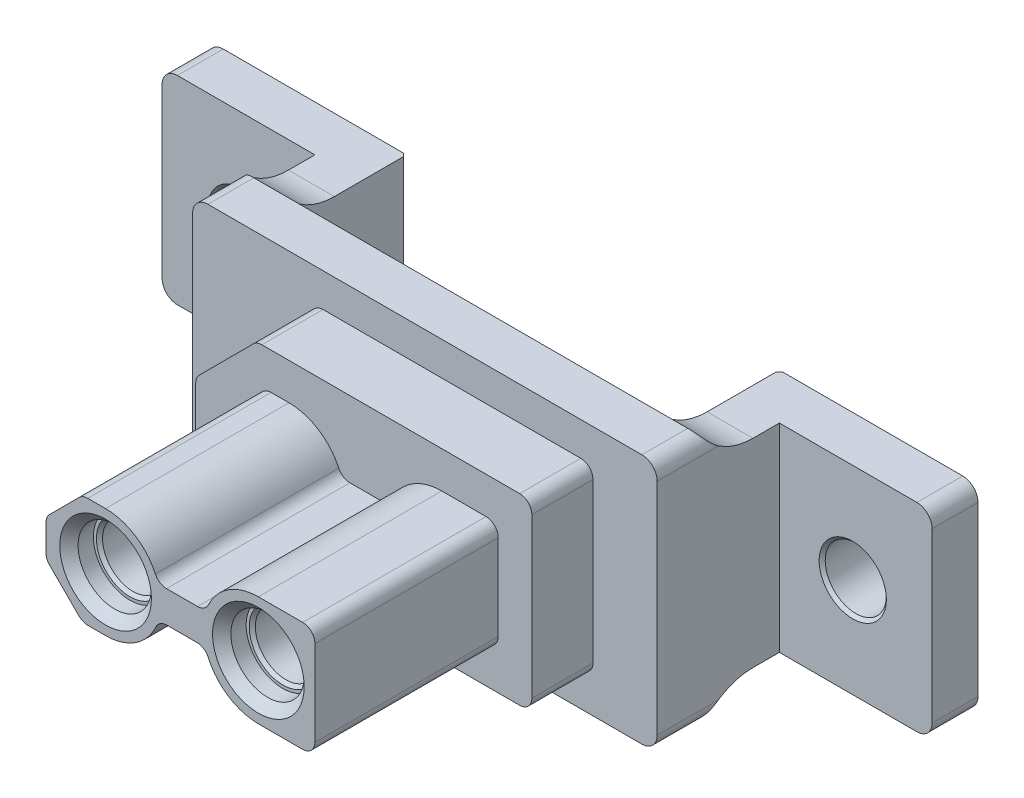
SolidWorks part; units mm, degrees
ref_plane "Спереди" through (0, 0, 0) normal (0, 0, 1) x (1, 0, 0)
ref_plane "Сверху" through (0, 0, 0) normal (0, 1, 0) x (1, 0, 0)
ref_plane "Справа" through (0, 0, 0) normal (1, 0, 0) x (0, 0, -1)
sketch "Эскиз1" plane through (0, 0, 0) normal (0, 0, 1) x (1, 0, 0)
  line L0 (-2.7412, 0) -> (2.2588, 0) construction
  line L1 (2.2588, 1.8) -> (3.7088, 1.8)
  line L2 (4.1088, 1.4) -> (4.1088, -1.4)
  line L3 (3.7088, -1.8) -> (2.2588, -1.8)
  line L4 (-0.7337, -0.5) -> (0.2513, -0.5)
  line L5 (-4.6912, 0.4343) -> (-4.6912, -0.4343)
  line L6 (-0.7472, 0.5294) -> (0.2648, 0.5294)
  line L7 (-2.7412, -0.5) -> (2.2588, -0.5) construction
  line L8 (-2.7412, 1.8) -> (-3.3255, 1.8)
  line L9 (-2.7412, -1.8) -> (-3.3255, -1.8)
  line L10 (-3.6084, 1.6828) -> (-4.574, 0.7172)
  line L11 (-3.6084, -1.6828) -> (-4.574, -0.7172)
  circle A0 centre (2.2588, 0) radius 1.2
  circle A1 centre (-2.7412, 0) radius 1.2
  arc A2 (-1.1097, 0.7604) -> (-2.7412, 1.8) centre (-2.7412, 0) ccw
  arc A3 (2.2588, 1.8) -> (0.6273, 0.7604) centre (2.2588, 0) ccw
  arc A4 (0.6163, -0.7364) -> (2.2588, -1.8) centre (2.2588, 0) ccw
  circle A5 centre (2.2588, 0) radius 1.8 construction
  circle A6 centre (-2.7412, 0) radius 1.8 construction
  arc A7 (-2.7412, -1.8) -> (-1.0987, -0.7364) centre (-2.7412, 0) ccw
  arc A8 (4.1088, -1.4) -> (3.7088, -1.8) centre (3.7088, -1.4) cw
  arc A9 (3.7088, 1.8) -> (4.1088, 1.4) centre (3.7088, 1.4) cw
  arc A10 (0.6163, -0.7364) -> (0.2513, -0.5) centre (0.2513, -0.9) ccw
  arc A11 (-0.7337, -0.5) -> (-1.0987, -0.7364) centre (-0.7337, -0.9) ccw
  arc A12 (-0.7472, 0.5294) -> (-1.1097, 0.7604) centre (-0.7472, 0.9294) cw
  arc A13 (0.6273, 0.7604) -> (0.2648, 0.5294) centre (0.2648, 0.9294) cw
  arc A14 (-3.6084, 1.6828) -> (-3.3255, 1.8) centre (-3.3255, 1.4) cw
  arc A15 (-4.574, 0.7172) -> (-4.6912, 0.4343) centre (-4.2912, 0.4343) ccw
  arc A16 (-4.574, -0.7172) -> (-4.6912, -0.4343) centre (-4.2912, -0.4343) cw
  arc A17 (-3.6084, -1.6828) -> (-3.3255, -1.8) centre (-3.3255, -1.4) ccw
  point P4 (4.0588, 0)
  point P16 (-2.7412, 0.5)
  point P17 (2.3588, 0.5)
  point P18 (-1.0412, 0)
  point P26 (-4.6912, 1.8)
  point P28 (-4.6912, -1.8)
  point P44 (-3.4912, 1.8)
  point P47 (-4.6912, 0.6)
  point P50 (-4.6912, -0.6)
  point P53 (-3.4912, -1.8)
  dimension "D2" = 2.4
  dimension "D3" = 2.4
  dimension "D8" = 0.4
  dimension "D1" = 5
  dimension "D6" = 8.8
  dimension "D7" = 1.85
  dimension "D4" = 0.6
  dimension "D5" = 0.5
extrude "Бобышка-Вытянуть1" add sketch "Эскиз1" along normal blind 6
sketch "Эскиз2" plane through (0, 0, 0) normal (0, 0, -1) x (-1, 0, 0)
  line L0 (-4.1088, 0) -> (4.6912, 0) construction
  line L5 (-4.1088, -1.4) -> (-4.1088, 1.4) construction
  line L6 (4.6912, 0.4343) -> (4.6912, -0.4343) construction
  line L7 (3.9084, 2.8828) -> (5.674, 1.1172)
  line L8 (-4.8088, 3) -> (3.6255, 3)
  line L9 (-5.2088, 2.6) -> (-5.2088, -2.6)
  line L10 (-4.8088, -3) -> (5.3912, -3)
  line L11 (5.7912, 0.8343) -> (5.7912, -2.6)
  line L12 (-5.2088, 3) -> (5.7912, -3) construction
  line L13 (-5.2088, -3) -> (5.7912, 3) construction
  circle A0 centre (-2.2588, 0) radius 1.2
  circle A1 centre (2.7412, 0) radius 1.2
  arc A2 (5.674, 1.1172) -> (5.7912, 0.8343) centre (5.3912, 0.8343) cw
  arc A3 (3.9084, 2.8828) -> (3.6255, 3) centre (3.6255, 2.6) ccw
  arc A4 (-4.8088, 3) -> (-5.2088, 2.6) centre (-4.8088, 2.6) ccw
  arc A5 (-5.2088, -2.6) -> (-4.8088, -3) centre (-4.8088, -2.6) ccw
  arc A6 (5.3912, -3) -> (5.7912, -2.6) centre (5.3912, -2.6) ccw
  point P6 (0, 0)
  point P12 (0.2912, 0)
  point P23 (5.7912, 1)
  point P26 (3.7912, 3)
  dimension "D3" = 0.4
  dimension "D1" = 11
  dimension "D2" = 6
extrude "Бобышка-Вытянуть2" add sketch "Эскиз2" along normal blind 2
sketch "Эскиз3" plane through (0, 0, -2) normal (0, 0, -1) x (-1, 0, 0)
  line L0 (-5.2088, 0) -> (5.7912, 0) construction
  line L1 (-5.2088, 2.6) -> (-5.2088, -2.6) construction
  line L2 (5.7912, -2.6) -> (5.7912, 0.8343) construction
  line L3 (5.7912, 0) -> (0.2912, -3) construction
  line L4 (-4.8088, -3) -> (5.3912, -3) construction
  line L5 (0.2912, -3) -> (0.2912, 5.0171) construction
  line L7 (-7.3088, 4.1) -> (7.8912, 4.1)
  line L8 (-7.3088, 4.1) -> (-7.3088, -4.1)
  line L9 (-7.3088, -4.1) -> (7.8912, -4.1)
  line L10 (7.8912, 4.1) -> (7.8912, -4.1)
  line L11 (-7.3088, 4.1) -> (7.8912, -4.1) construction
  line L12 (-7.3088, -4.1) -> (7.8912, 4.1) construction
  circle A1 centre (2.7412, 0) radius 1.2
  circle A2 centre (-2.2588, 0) radius 1.2
  point P7 (0.2912, 0)
  dimension "D1" = 8.2
  dimension "D2" = 15.2
extrude "Бобышка-Вытянуть3" add sketch "Эскиз3" along normal blind 1.5
sketch "Эскиз4" plane through (0, 0, -3.5) normal (0, 0, -1) x (-1, 0, 0)
  line L0 (-7.3088, 0) -> (7.8912, 0) construction
  line L1 (-7.3088, 4.1) -> (-7.3088, -4.1) construction
  line L2 (7.8912, -4.1) -> (7.8912, 4.1) construction
  line L3 (0.2912, -3.838) -> (0.2912, 4.1) construction
  line L4 (-5.8088, 3.25) -> (-7.3088, 3.25)
  line L5 (-5.8088, 3.25) -> (-5.8088, -3.25)
  line L6 (-5.8088, -3.25) -> (-7.3088, -3.25)
  line L7 (-7.3088, 3.25) -> (-7.3088, -3.25)
  line L8 (-5.8088, 3.25) -> (-7.3088, -3.25) construction
  line L9 (-5.8088, -3.25) -> (-7.3088, 3.25) construction
  line L10 (7.8912, 4.1) -> (-7.3088, 4.1) construction
  line L11 (6.3912, -3.25) -> (7.8912, -3.25)
  line L12 (7.8912, 3.25) -> (7.8912, -3.25)
  line L13 (6.3912, 3.25) -> (7.8912, 3.25)
  line L14 (6.3912, 3.25) -> (6.3912, -3.25)
  point P6 (-6.5588, 0)
  dimension "D1" = 1.5
  dimension "D2" = 6.5
extrude "Бобышка-Вытянуть4" add sketch "Эскиз4" along normal blind 4
sketch "Эскиз5" plane through (-7.8912, 0, 0) normal (-1, 0, 0) x (0, 0, 1)
  line L0 (-7.5, -3.25) -> (-3.5, -3.25) construction
  line L1 (-7.5, 3.25) -> (-6, 3.25)
  line L2 (-7.5, 3.25) -> (-7.5, -3.25)
  line L3 (-7.5, -3.25) -> (-6, -3.25)
  line L4 (-6, 3.25) -> (-6, -3.25)
  dimension "D1" = 1.5
extrude "Бобышка-Вытянуть5" add sketch "Эскиз5" along normal blind 5
sketch "Эскиз6" plane through (7.3088, 0, 0) normal (1, 0, 0) x (0, 0, -1)
  line L1 (7.5, 3.25) -> (6, 3.25)
  line L2 (7.5, 3.25) -> (7.5, -3.25)
  line L3 (7.5, -3.25) -> (6, -3.25)
  line L4 (6, 3.25) -> (6, -3.25)
  dimension "D1" = 1.5
extrude "Бобышка-Вытянуть6" add sketch "Эскиз6" along normal blind 5
fillet "Скругление1" radius 2 4 edges at (-7.1412, 3.25, -3.5) (-7.1412, -3.25, -3.5) (6.5588, -3.25, -3.5) (6.5588, 3.25, -3.5)
fillet "Скругление2" radius 0.5 10 edges at (-12.8912, -3.25, -6.75) (-12.8912, 3.25, -6.75) (12.3088, 3.25, -6.75) (12.3088, -3.25, -6.75) (7.3088, -4.1, -2.75) (-7.8912, -4.1, -2.75) (-7.8912, 4.1, -2.75) (7.3088, 4.1, -2.75) (-6.3912, 0, -3.5) (5.8088, 0, -3.5)
sketch "Эскиз7" plane through (0, 0, -6) normal (0, 0, 1) x (1, 0, 0)
  line L0 (-12.8912, 0) -> (12.3088, 0) construction
  line L1 (-12.8912, -2.75) -> (-12.8912, 2.75) construction
  line L2 (12.3088, 2.75) -> (12.3088, -2.75) construction
  line L3 (-0.2912, 4.1) -> (-0.2912, -4.1) construction
  line L4 (-7.3912, 4.1) -> (6.8088, 4.1) construction
  line L5 (6.8088, -4.1) -> (-7.3912, -4.1) construction
  circle A0 centre (-10.2912, 0) radius 1
  circle A1 centre (9.7088, 0) radius 1
  dimension "D3" = 2
  dimension "D4" = 2
  dimension "D1" = 20
  dimension "D2" = 10
extrude "Вырез-Вытянуть1" cut sketch "Эскиз7" against normal blind 5
chamfer "Фаска1" distance 0.1 angle 45 4 edges at (10.7088, 0, -6) (-9.2912, 0, -6) (5.8088, 0, -7.5) (-6.3912, 0, -7.5)
sketch "Эскиз8" plane through (0, 0, -3.5) normal (0, 0, -1) x (-1, 0, 0)
  line L0 (-2.2588, 2) -> (2.7412, 2)
  line L1 (-2.2588, 2) -> (-3.2588, 2)
  line L2 (-4.2588, -1) -> (-4.2588, 1)
  line L3 (2.7412, -2) -> (-3.2588, -2)
  arc A0 (2.7412, -2) -> (2.7412, 2) centre (2.7412, 0) ccw
  arc A4 (-3.2588, -2) -> (-4.2588, -1) centre (-3.2588, -1) cw
  arc A5 (-4.2588, 1) -> (-3.2588, 2) centre (-3.2588, 1) cw
  circle M3 centre (-2.2588, 0) radius 1.2
  circle M4 centre (2.7412, 0) radius 1.2
  dimension "D1" = 1
  dimension "D2" = 4
extrude "Вырез-Вытянуть2" cut sketch "Эскиз8" against normal blind 2 contours L3 A0 L0 L1 L2 M3 M4 region at (-0.0347, 0, -3.5)
sketch "Эскиз9" plane through (0, 0, -1.5) normal (0, 0, -1) x (-1, 0, 0)
  circle A0 centre (-2.2588, 0) radius 1.2
  circle A1 centre (2.7412, 0) radius 1.2
extrude "Бобышка-Вытянуть7" add sketch "Эскиз9" against normal offset from surface 0.8 and the other way offset from surface 12.4 up to face at (3.4588, 0, 6) other way up to face at (3.4588, 0, 6)
sketch "Эскиз10" plane through (0, 0, 5.2) normal (0, 0, 1) x (1, 0, 0)
  circle A0 centre (-2.7412, 0) radius 1
  circle A1 centre (2.2588, 0) radius 1
  dimension "D1" = 2
  dimension "D2" = 2
extrude "Вырез-Вытянуть3" cut sketch "Эскиз10" against normal blind 6
chamfer "Фаска2" distance 0.1 angle 45 2 edges at (3.2588, 0, 5.2) (-1.7412, 0, 5.2)
chamfer "Фаска3" distance 0.3 angle 45 2 edges at (3.4588, 0, 6) (-1.5412, 0, 6)
sketch "Эскиз11" plane through (0, 0, -6.4) normal (0, 0, -1) x (-1, 0, 0)
  circle A0 centre (-2.2588, 0) radius 0.5
  circle A1 centre (2.7412, 0) radius 0.5
  circle A2 centre (-2.2588, 0) radius 1.2 construction
  circle A3 centre (2.7412, 0) radius 1.2 construction
  dimension "D1" = 0.7
  dimension "D2" = 0.7
extrude "Вырез-Вытянуть4" cut sketch "Эскиз11" against normal up to surface (4.9 mm away) up to face at (1.3278, 0, -1.5)
sketch "Эскиз12" plane through (0, 0, -6.4) normal (0, 0, -1) x (-1, 0, 0)
  line L0 (-3.4588, 0) -> (3.9412, 0)
  line L1 (3.9412, 0) -> (4.5951, 3.2423)
  line L2 (4.5951, 3.2423) -> (-4.6585, 3.2423)
  line L3 (-4.6585, 3.2423) -> (-3.4588, 0)
  circle A0 centre (-2.2588, 0) radius 1.2 construction
  circle A1 centre (-2.2588, 0) radius 1.2 construction
  circle A2 centre (2.7412, 0) radius 1.2 construction
extrude "Вырез-Вытянуть9" cut sketch "Эскиз12" against normal up to surface (2.9 mm away) up to face at (-0.2912, 0, -3.5)
fillet "Скругление3" radius 0.1 8 edges at (-3.5912, 0, -6.4) (-1.8912, 0, -6.4) (-2.7412, -0.5, -6.4) (-2.7412, -1.2, -6.4) (2.2588, -1.2, -6.4) (1.4088, 0, -6.4) (3.1088, 0, -6.4) (2.2588, -0.5, -6.4)
chamfer "Фаска4" distance 0.3 angle 45 2 edges at (-3.2412, 0, -1.5) (1.7588, 0, -1.5)
chamfer "Фаска5" distance 0.4 angle 45 2 edges at (-1.7412, 0, -0.8) (3.2588, 0, -0.8)
sketch "Эскиз13" plane through (0, 0, -3.5) normal (0, 0, -1) x (-1, 0, 0)
  text T0 "+" font "@BIZ UDPゴシック" height 2.5
  text T1 "-"
extrude "Бобышка-Вытянуть8" add sketch "Эскиз13" along normal blind 0.1
sketch "Эскиз14" plane through (0, 0, -3.5) normal (0, 0, -1) x (-1, 0, 0)
  text T0 "Amass" font "ＭＳ ゴシック" height 1.5
extrude "Бобышка-Вытянуть13" add sketch "Эскиз14" along normal blind 0.1
